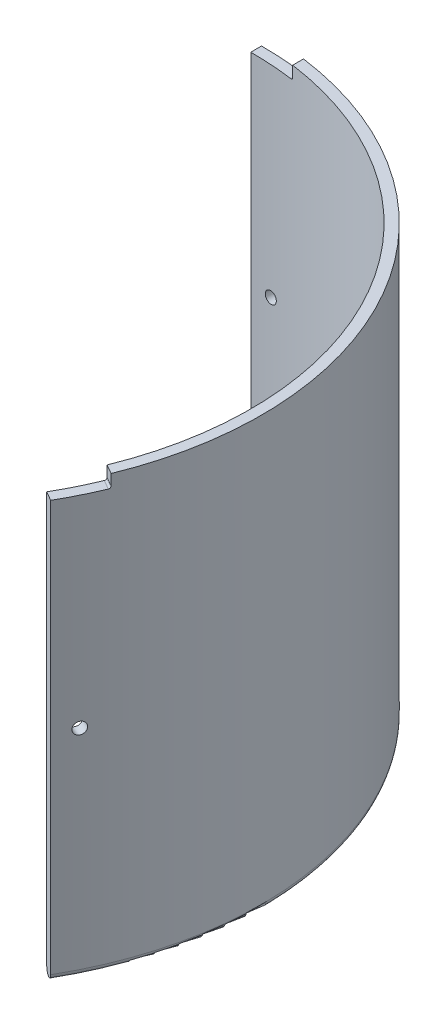
SolidWorks part; units mm, degrees
ref_plane "Front Plane" through (0, 0, 0) normal (0, 0, 1) x (1, 0, 0)
ref_plane "Top Plane" through (0, 0, 0) normal (0, 1, 0) x (1, 0, 0)
ref_plane "Right Plane" through (0, 0, 0) normal (1, 0, 0) x (0, 0, -1)
sketch "Sketch1" plane through (0, 0, 0) normal (0, 1, 0) x (1, 0, 0)
  line L0 (0, 150) -> (0, 155)
  line L1 (129.9038, -75) -> (134.2339, -77.5)
  line L2 (0, 150) -> (0, 0) construction
  line L3 (0, 0) -> (154.1759, -89.0135) construction
  arc A0 (134.2339, -77.5) -> (0, 155) centre (0, 0) ccw
  arc A1 (129.9038, -75) -> (0, 150) centre (0, 0) ccw
  dimension "D1" = 150
  dimension "D2" = 5
  dimension "D3" = 120
extrude "Boss-Extrude1" add sketch "Sketch1" along normal blind 200
sketch "Sketch3" plane through (0, 200, 0) normal (0, 1, 0) x (1, 0, 0)
  line L0 (0, 0) -> (0, 186.0481) construction
  line L1 (0, 0) -> (189.96, -109.6735) construction
  line L2 (21, 153.5708) -> (21, 148.5227)
  line L3 (143.4962, -58.5989) -> (139.1245, -56.0748)
  line L4 (134.2339, -77.5) -> (129.9038, -75)
  line L5 (0, 155) -> (0, 150)
  arc A1 (129.9038, -75) -> (139.1245, -56.0748) centre (0, 0) ccw
  arc A2 (134.2339, -77.5) -> (143.4962, -58.5989) centre (0, 0) ccw
  arc A3 (134.2339, -77.5) -> (0, 155) centre (0, 0) ccw construction
  arc A4 (129.9038, -75) -> (0, 150) centre (0, 0) ccw construction
  arc A5 (21, 148.5227) -> (0, 150) centre (0, 0) ccw
  arc A6 (21, 153.5708) -> (0, 155) centre (0, 0) ccw
  dimension "D1" = 120
  dimension "D2" = 21
  dimension "D3" = 21
extrude "Cut-Extrude1" cut sketch "Sketch3" against normal blind 6
fillet "Fillet1" radius 1 2 edges at (21, 194, -151.0468) (141.3103, 194, 57.3369)
fillet "Fillet2" radius 2.5 2 edges at (134.2339, 0, -77.5) (129.9038, 0, -75)
hole_wizard "M5 Clearance Hole1" positions "3DSketch1" profile "Sketch4" hole size "M5" standard "ANSI Metric" end condition up to next
sketch3d "3DSketch1"
  point P0 (138.9543, 100, 68.6783)
  point P2 (10, 100, -154.6771)
  dimension "D2" = 100
  dimension "D1" = 100
  dimension "D3" = 10
  dimension "D4" = 10
sketch "Sketch4" plane through (138.9543, 100, 68.6783) normal (0, 1, 0) x (0.4431, 0, -0.8965)
  line L0 (0, 0) -> (0, 5)
  line L1 (0, 5) -> (2.75, 5)
  line L2 (2.75, 5) -> (2.75, 0)
  line L5 (2.75, 0) -> (0, 0)
  line L11 (0, -6.35) -> (0, 107.95) construction
  dimension "Thru Hole Dia." = 5.5
  dimension "Thru Hole Depth" = 5
equation "\"D2@Sketch3\"=20+1"
equation "\"D3@Sketch3\"=\"D2@Sketch3\""
equation "\"D2@3DSketch1\"=\"D1@3DSketch1\""
equation "\"D4@3DSketch1\"=\"D3@3DSketch1\""
